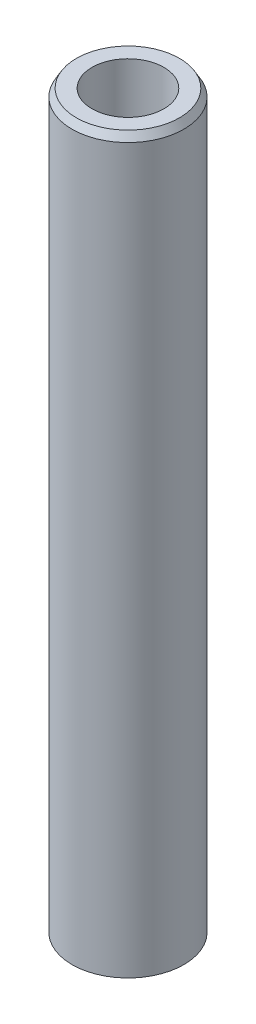
SolidWorks part; units mm, degrees
ref_plane "Front Plane" through (0, 0, 0) normal (0, 0, 1) x (1, 0, 0)
ref_plane "Top Plane" through (0, 0, 0) normal (0, 1, 0) x (1, 0, 0)
ref_plane "Right Plane" through (0, 0, 0) normal (1, 0, 0) x (0, 0, -1)
sketch "Sketch1" plane through (0, 0, 0) normal (0, 1, 0) x (1, 0, 0)
  circle A0 centre (0, 0) radius 37.5
  dimension "SHAFT_OD" = 75
extrude "Boss-Extrude1" add sketch "Sketch1" along normal blind 492.9825
sketch "Sketch2" plane through (0, 0, 0) normal (0, 1, 0) x (1, 0, 0)
  circle A0 centre (0, 0) radius 24.0961
  dimension "BORE_D" = 48.1922
extrude "Cut-Extrude1" cut sketch "Sketch2" along normal through all
chamfer "Chamfer1" distance 5.1236 angle 30 2 edges at (0, 492.9825, 37.5) (0, 0, 37.5) first distance on face at (0, 492.9825, 37.5) first distance on face at (0, 0, 24.0961)
